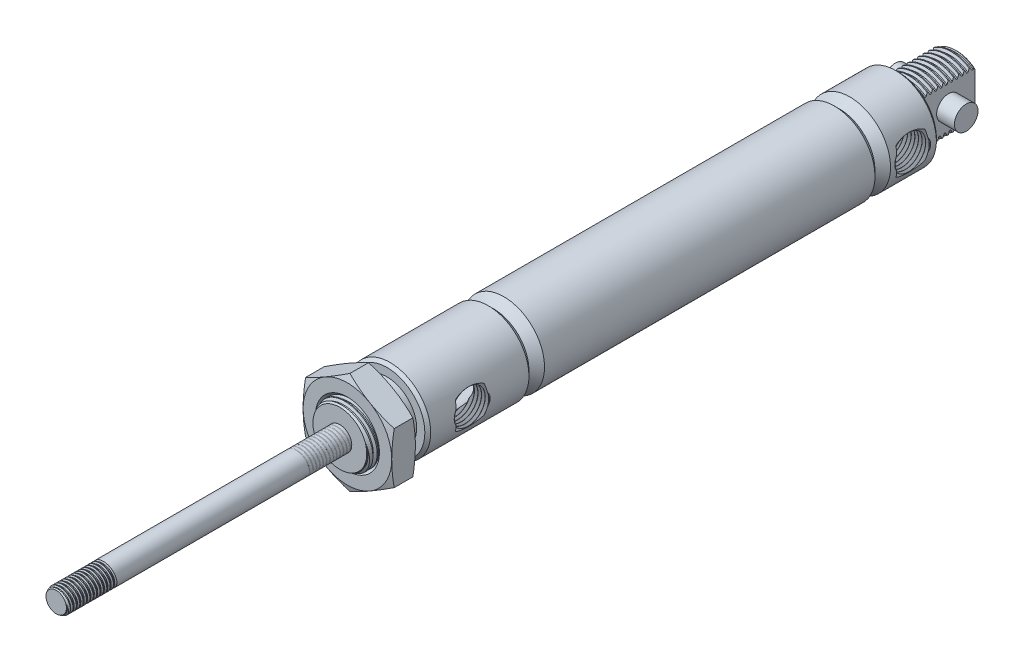
SolidWorks part; units mm, degrees
ref_plane "Front" through (0, 0, 0) normal (0, 0, 1) x (1, 0, 0)
ref_plane "Top" through (0, 0, 0) normal (0, 1, 0) x (1, 0, 0)
ref_plane "Right" through (0, 0, 0) normal (1, 0, 0) x (0, 0, -1)
sketch "Sketch1" plane through (0, 0, 0) normal (1, 0, 0) x (0, 0, -1)
  line L0 (-89.281, 0) -> (89.281, 0) construction
  line L1 (-76.581, -7.9375) -> (-76.581, 0) construction
  line L2 (-76.581, 7.9375) -> (-63.881, 7.9375) construction
  line L3 (-63.881, 0) -> (-63.881, 10.922)
  line L4 (-63.881, 10.922) -> (89.281, 10.922)
  line L5 (73.533, 10.922) -> (73.533, 7.9375) construction
  line L6 (73.533, 7.9375) -> (89.281, 7.9375) construction
  line L7 (89.281, 10.922) -> (89.281, 0)
  line L8 (89.281, 0) -> (105.029, 0) construction
  line L9 (-76.581, -7.9375) -> (-63.881, -7.9375) construction
  line L10 (-63.881, -7.9375) -> (-63.881, -10.922) construction
  line L11 (-63.881, -10.922) -> (89.281, -10.922) construction
  line L12 (73.533, -10.922) -> (73.533, -7.9375) construction
  line L13 (73.533, -7.9375) -> (89.281, -7.9375) construction
  line L14 (-66.167, 9.525) -> (-66.167, 0) construction
  line L18 (-76.581, 3.175) -> (-89.281, 3.175) construction
  line L19 (-89.281, 3.175) -> (-89.281, -3.175) construction
  line L20 (-89.281, -3.175) -> (-76.581, -3.175) construction
  line L24 (-76.581, 4.7625) -> (-66.167, 4.7625) construction
  line L25 (89.281, 0) -> (89.281, -10.922) construction
  line L26 (-76.581, 0) -> (-76.581, 7.9375) construction
  line L28 (-63.881, 0) -> (89.281, 0)
  line L29 (-71.374, 4.7625) -> (-71.374, 7.9375) construction
  line L30 (-63.881, 9.525) -> (-66.167, 9.525) construction
  dimension "D1" = 19.05
  dimension "J Flat" = 15.875
  dimension "E OD" = 21.844
  dimension "K Flat Depth" = 15.748
  dimension "RM Pilot" = 15.875
  dimension "G Pilot Length" = 12.7
  dimension "Shaft Dia" = 6.35
  dimension "A Thread Length" = 12.7
  dimension "Total Length" = 178.562
  dimension "V Pilot Length" = 2.286
revolve "Revolve1" add sketch "Sketch1" angle 360 about L8 reverse direction yes
sketch "Sketch58" plane through (0, 0, 0) normal (1, 0, 0) x (0, 0, -1)
  line L0 (89.281, 0) -> (105.029, 0) construction
  line L1 (73.533, 10.922) -> (89.281, 10.922)
  line L2 (73.533, 10.922) -> (73.533, 7.9375)
  line L3 (73.533, 7.9375) -> (89.281, 7.9375)
  line L4 (89.281, 10.922) -> (89.281, 7.9375)
  line L5 (89.281, 0) -> (105.029, 0) construction
revolve "Cut-Revolve25" cut sketch "Sketch58" angle 360 about L5
sketch "Sketch59" plane through (0, 0, -89.281) normal (0, 0, -1) x (-1, 0, 0)
  line L0 (-4.7625, -7.9375) -> (4.7625, 7.9375) construction
  line L1 (-4.7625, 7.9375) -> (4.7625, 7.9375)
  line L2 (-4.7625, 7.9375) -> (-4.7625, -7.9375)
  line L3 (-4.7625, -7.9375) -> (4.7625, -7.9375)
  line L4 (4.7625, 7.9375) -> (4.7625, -7.9375)
  dimension "D1" = 9.525
extrude "Cut-Extrude3" cut sketch "Sketch59" against normal up to surface (15.748 mm away) flip side to cut up to face at (7.9375, 0, -73.533)
chamfer "Chamfer1" distance 0.7874 angle 45 4 edges at (-10.922, 0, 63.881) (10.922, 0, -73.533) (0, 7.9375, -89.281) (0, -7.9375, -89.281)
sketch "Sketch4" plane through (0, 0, 0) normal (1, 0, 0) x (0, 0, -1)
  line L0 (-76.581, 0) -> (-76.581, 7.9375) construction
  line L1 (-89.281, 0) -> (89.281, 0) construction
  line L2 (-63.881, 0) -> (-63.881, 10.922) construction
  line L3 (-76.581, 7.9375) -> (-63.881, 7.9375) construction
  line L4 (-76.581, 0) -> (-76.581, 7.9375)
  line L5 (-76.581, 0) -> (-63.881, 0)
  line L6 (-63.881, 0) -> (-63.881, 7.9375)
  line L7 (-76.581, 7.9375) -> (-63.881, 7.9375)
  line L8 (-76.581, -7.9375) -> (-63.881, -7.9375) construction
  line L9 (-76.581, -7.9375) -> (-63.881, -7.9375) construction
revolve "Revolve2" add sketch "Sketch4" angle 360 about L5
sketch "Sketch5" plane through (0, 0, 0) normal (1, 0, 0) x (0, 0, -1)
  line L0 (-76.581, 7.9375) -> (-76.581, -7.9375) construction
  line L1 (-76.581, -7.9375) -> (-75.1699, -7.9375) construction
  line L2 (-75.1699, -7.9375) -> (-76.581, 7.9375) construction
  line L3 (-76.581, 7.9375) -> (-76.4053, 7.9531) construction
  line L4 (-76.4053, 7.9531) -> (-75.1754, 8.0624)
  line L5 (-75.1754, 8.0624) -> (-75.547, 7.2626)
  line L6 (-75.547, 7.2626) -> (-75.8984, 7.2314)
  line L7 (-75.8984, 7.2314) -> (-76.4053, 7.9531)
  line L8 (-75.7904, 8.0078) -> (-75.7227, 7.247) construction
  line L9 (-76.581, 7.9375) -> (-75.7841, 7.9375) construction
  line L10 (-75.7841, 7.9375) -> (-74.373, -7.9375) construction
  line L11 (-74.373, -7.9375) -> (-75.1699, -7.9375) construction
  line L12 (-76.581, 0) -> (-76.581, 7.9375) construction
  line L13 (-76.581, 7.9375) -> (-63.881, 7.9375) construction
  line L14 (-76.581, -7.9375) -> (-63.881, -7.9375) construction
  line L15 (-76.581, -0.1335) -> (-73.5761, 0.1335) construction
  point P19 (-75.0786, 0)
  dimension "D1" = 0.1764
  dimension "D2" = 0.3528
  dimension "Thread Pitch" = 1.4111
  dimension "D4" = 60
  dimension "D5" = 1.4111
revolve "Cut-Revolve2" cut sketch "Sketch5" angle 360 about L15
sketch "Sketch6" plane through (0, 0, 0) normal (1, 0, 0) x (0, 0, -1)
  line L0 (-76.581, 7.2314) -> (-75.358, 7.9375)
  line L1 (-75.358, 7.9375) -> (-76.581, 7.9375)
  line L2 (-76.581, 7.9375) -> (-76.581, 7.2314)
  line L3 (0, 0) -> (-76.581, 0) construction
  line L4 (-76.581, 0) -> (-76.581, 7.2314) construction
  line L5 (-76.581, 7.9375) -> (-63.881, 7.9375) construction
  line L6 (-76.581, 0) -> (-76.581, 7.9375) construction
  line L7 (-75.8984, 7.2314) -> (-76.581, 7.2314) construction
  dimension "D1" = 60
revolve "Cut-Revolve3" cut sketch "Sketch6" angle 360 about L3
pattern_linear "LPattern2" count 2 spacing 1.4111 along (0, 0, 1) count 9 spacing 1.4111 along (0, 0, -1) of "Cut-Revolve2"
sketch "Sketch53" plane through (0, 0, 0) normal (1, 0, 0) x (0, 0, -1)
  line L0 (-76.581, 0) -> (-63.881, 0) construction
  line L1 (-63.881, 7.9375) -> (-66.167, 7.9375)
  line L2 (-63.881, 7.9375) -> (-63.881, 0)
  line L3 (-63.881, 0) -> (-66.167, 0)
  line L4 (-66.167, 7.9375) -> (-66.167, 0)
  line L5 (-66.167, 9.525) -> (-66.167, 0) construction
  line L6 (-76.581, 7.9375) -> (-63.881, 7.9375) construction
  line L7 (-63.881, 0) -> (-63.881, 10.922) construction
revolve "Revolve4" add sketch "Sketch53" angle 360 about L3
sketch "Sketch62" plane through (0, 0, 0) normal (1, 0, 0) x (0, 0, -1)
  line L0 (73.533, 7.9375) -> (73.533, -7.9375) construction
  line L1 (73.533, -7.9375) -> (74.9441, -7.9375) construction
  line L2 (74.9441, -7.9375) -> (73.533, 7.9375) construction
  line L3 (73.533, 7.9375) -> (73.7087, 7.9531) construction
  line L4 (73.7087, 7.9531) -> (74.9386, 8.0624)
  line L5 (74.9386, 8.0624) -> (74.567, 7.2626)
  line L6 (74.567, 7.2626) -> (74.2156, 7.2314)
  line L7 (74.2156, 7.2314) -> (73.7087, 7.9531)
  line L8 (74.3913, 7.247) -> (74.3236, 8.0078) construction
  line L9 (73.533, 7.9375) -> (74.3299, 7.9375) construction
  line L10 (74.3299, 7.9375) -> (75.741, -7.9375) construction
  line L11 (75.741, -7.9375) -> (74.9441, -7.9375) construction
  line L12 (73.533, -0.1335) -> (76.5379, 0.1335) construction
  line L13 (73.533, 7.9375) -> (89.281, 7.9375) construction
  line L14 (73.533, 10.922) -> (73.533, 7.9375) construction
  line L15 (73.533, -7.9375) -> (89.281, -7.9375) construction
  point P13 (75.0354, 0)
  dimension "D1" = 60
  dimension "D2" = 0.3528
  dimension "D3" = 0.1764
  dimension "D4" = 1.4111
  dimension "D5" = 1.4111
revolve "Cut-Revolve26" cut sketch "Sketch62" angle 360 about L12
pattern_linear "LPattern5" count 11 spacing 1.4111 along (0, 0, -1) of "Cut-Revolve26"
sketch "Sketch60" plane through (0, 0, 0) normal (1, 0, 0) x (0, 0, -1)
  line L0 (-63.881, 0) -> (89.281, 0) construction
  line L1 (89.281, 10.922) -> (89.281, 0) construction
  circle A0 centre (82.169, 0) radius 3.175
  dimension "D2" = 6.35
  dimension "D1" = 7.112
extrude "Extrude2" add sketch "Sketch60" along normal mid plane 19.05
sketch "Sketch7" plane through (0, 0, 0) normal (1, 0, 0) x (0, 0, -1)
  line L0 (-76.581, 3.2004) -> (-60.706, 3.2004)
  line L1 (-60.706, 3.2004) -> (-60.706, 6.3627)
  line L2 (-60.706, 9.525) -> (-18.542, 9.525) construction
  line L3 (-12.192, 9.525) -> (51.308, 9.525)
  line L4 (51.308, 0) -> (-76.581, 0)
  line L5 (-76.581, 0) -> (-76.581, 3.2004)
  line L6 (-76.581, 0) -> (-76.581, 7.9375) construction
  line L7 (-63.881, 0) -> (89.281, 0) construction
  line L8 (51.308, 0) -> (105.029, 0) construction
  line L9 (-63.881, 0) -> (-63.881, 10.922) construction
  line L10 (51.308, 9.525) -> (51.308, 0)
  line L11 (56.261, 10.922) -> (57.658, 9.525)
  line L12 (-60.706, 6.3627) -> (-18.542, 6.3627)
  line L13 (-18.542, 6.3627) -> (-18.542, 9.525)
  line L14 (-60.706, 6.3627) -> (-60.706, 9.525) construction
  line L15 (-18.542, 9.525) -> (-12.192, 9.525)
  line L17 (57.658, 9.525) -> (57.658, 8.128)
  line L18 (57.658, 8.128) -> (60.452, 10.922)
  line L19 (60.452, 10.922) -> (56.261, 10.922)
  line L20 (57.658, 9.525) -> (57.658, 10.922) construction
  line L21 (-63.881, 10.922) -> (89.281, 10.922) construction
  line L22 (73.533, 10.922) -> (73.533, 7.9375) construction
  line L23 (-36.703, 10.922) -> (-35.306, 9.525)
  line L24 (-35.306, 9.525) -> (-35.306, 8.128)
  line L25 (-35.306, 8.128) -> (-32.512, 10.922)
  line L26 (-32.512, 10.922) -> (-36.703, 10.922)
  line L27 (-35.306, 9.525) -> (-35.306, 10.922) construction
  line L28 (-76.581, 3.175) -> (-89.281, 3.175) construction
  dimension "D1" = 0.0254
  dimension "Bore Dia" = 19.05
  dimension "D2" = 6.35
  dimension "D3" = 45
  dimension "Stroke" = 63.5
  dimension "D4" = 3.175
  dimension "D5" = 6.35
  dimension "D6" = 15.875
  dimension "D7" = 28.575
revolve "Cut-Revolve5" cut sketch "Sketch7" angle 360 about L8
sketch "Sketch8" plane through (0, 0, 0) normal (1, 0, 0) x (0, 0, -1)
  line L2 (44.958, 9.4742) -> (51.308, 9.4742)
  line L3 (51.308, 9.4742) -> (51.308, 0)
  line L4 (-89.281, 3.175) -> (-89.281, -3.175) construction
  line L6 (-89.281, 3.175) -> (-89.281, 0)
  line L7 (51.308, 0) -> (-89.281, 0)
  line L8 (-89.281, 0) -> (89.281, 0) construction
  line L9 (-12.192, 9.525) -> (51.308, 9.525) construction
  line L11 (51.308, 9.525) -> (51.308, 0) construction
  line L15 (44.958, 3.175) -> (44.958, 9.4742)
  line L16 (44.958, 3.175) -> (-89.281, 3.175)
  dimension "D1" = 0.0508
  dimension "D2" = 6.35
revolve "Revolve3" add sketch "Sketch8" angle 360 about L7
sketch "Sketch10" plane through (0, 0, 0) normal (1, 0, 0) x (0, 0, -1)
  line L0 (-89.281, 3.175) -> (-89.281, -3.175) construction
  line L1 (-89.281, -3.175) -> (-88.3739, -3.175) construction
  line L2 (-88.3739, -3.175) -> (-89.281, 3.175) construction
  line L3 (-89.281, 3.175) -> (-89.1687, 3.191) construction
  line L4 (-89.1687, 3.191) -> (-88.383, 3.3033)
  line L5 (-88.383, 3.3033) -> (-88.5942, 2.7771)
  line L6 (-88.5942, 2.7771) -> (-88.8187, 2.7451)
  line L7 (-88.8187, 2.7451) -> (-89.1687, 3.191)
  line L8 (-88.7759, 3.2472) -> (-88.7064, 2.7611) construction
  line L9 (-89.281, 3.175) -> (-88.7656, 3.175) construction
  line L10 (-88.7656, 3.175) -> (-87.8584, -3.175) construction
  line L11 (-87.8584, -3.175) -> (-88.3739, -3.175) construction
  line L12 (-89.281, 3.175) -> (-89.281, -3.175) construction
  line L13 (-76.581, 3.175) -> (-89.281, 3.175) construction
  line L14 (-89.281, -3.175) -> (-76.581, -3.175) construction
  line L15 (-89.281, -0.1384) -> (-87.343, 0.1384) construction
  point P19 (-88.312, 0)
  dimension "D1" = 0.1134
  dimension "D2" = 0.2268
  dimension "Shaft Thread Pitch" = 0.9071
  dimension "D4" = 0.9071
  dimension "D5" = 60
revolve "Cut-Revolve6" cut sketch "Sketch10" angle 360 about L15
sketch "Sketch11" plane through (0, 0, 0) normal (1, 0, 0) x (0, 0, -1)
  line L0 (-89.281, 3.175) -> (-88.5363, 3.175)
  line L1 (-88.5363, 3.175) -> (-89.281, 2.7451)
  line L2 (-89.281, 2.7451) -> (-89.281, 3.175)
  line L3 (0, 0) -> (-89.281, 0) construction
  line L4 (-89.281, 0) -> (-89.281, 2.7451) construction
  line L5 (-76.581, 3.175) -> (-89.281, 3.175) construction
  line L6 (-89.281, 3.175) -> (-89.281, -3.175) construction
  line L7 (-88.8187, 2.7451) -> (-89.281, 2.7451) construction
  dimension "D1" = 30
revolve "Cut-Revolve7" cut sketch "Sketch11" angle 360 about L3
pattern_linear "LPattern3" count 2 spacing 0.9071 along (0, 0, 1) count 14 spacing 0.9071 along (0, 0, -1) of "Cut-Revolve6"
pattern_linear "LPattern4" count 2 spacing 63.5 along (0, 0, 1) of bodies 122
ref_plane "Plane4" through (0, 0, -66.421) normal (0, 0, -1) x (-1, 0, 0)
ref_axis "Axis3" through (0, -15.123, -66.421) along (0, 1, 0)
ref_plane "Plane6" through (0, 0, -66.421) normal (0, 0, 1) x (1, 0, 0)
sketch "Sketch13" plane through (-356.4319, -1.7517, -66.421) normal (0, 0, 1) x (1, 0, 0)
  line L0 (355.9239, 1.7517) -> (355.9239, 5.9543)
  line L1 (355.9239, 5.9543) -> (356.3686, 6.7833) construction
  line L2 (356.3686, 6.7833) -> (356.8642, 5.9837) construction
  line L3 (356.8642, 5.9837) -> (357.3089, 6.8127) construction
  line L4 (357.3089, 6.8127) -> (357.8045, 6.013) construction
  line L5 (356.8811, 6.0153) -> (357.2919, 6.781)
  line L6 (357.2919, 6.781) -> (357.3278, 6.7822)
  line L7 (357.3278, 6.7822) -> (357.7856, 6.0435)
  line L8 (357.7856, 6.0435) -> (357.8214, 6.0446)
  line L9 (355.9239, 5.9543) -> (357.8045, 6.013) construction
  line L10 (356.3686, 6.7833) -> (357.3089, 6.8127) construction
  line L11 (356.1462, 6.3688) -> (357.5567, 6.4128) construction
  line L12 (355.9239, 1.7517) -> (351.7213, 1.7517) construction
  line L13 (357.8214, 6.0446) -> (358.2322, 6.8104)
  line L14 (355.9409, 5.9859) -> (356.3516, 6.7517)
  line L15 (356.3516, 6.7517) -> (356.3875, 6.7528)
  line L16 (356.3875, 6.7528) -> (356.8453, 6.0141)
  line L17 (356.8453, 6.0141) -> (356.8811, 6.0153)
  line L18 (356.1462, 6.3688) -> (355.9239, 6.3618) construction
  line L19 (355.9239, 6.3618) -> (355.9239, 5.9543) construction
  line L20 (356.1462, -2.8653) -> (355.9239, -2.8584) construction
  line L21 (355.9409, 5.9859) -> (355.9239, 5.9543)
  line L22 (358.2322, 6.8104) -> (358.268, 6.8116)
  line L23 (358.268, 6.8116) -> (358.7258, 6.0729)
  line L24 (358.7258, 6.0729) -> (358.7617, 6.074)
  line L25 (358.7617, 6.074) -> (359.1725, 6.8398)
  line L26 (359.1725, 6.8398) -> (359.2083, 6.8409)
  line L27 (359.2083, 6.8409) -> (359.6661, 6.1023)
  line L28 (359.6661, 6.1023) -> (359.702, 6.1034)
  line L29 (359.702, 6.1034) -> (360.1128, 6.8692)
  line L30 (360.1128, 6.8692) -> (360.1486, 6.8703)
  line L31 (360.1486, 6.8703) -> (360.6064, 6.1317)
  line L32 (360.6064, 6.1317) -> (360.6423, 6.1328)
  line L33 (360.6423, 6.1328) -> (361.053, 6.8986)
  line L34 (361.053, 6.8986) -> (361.0889, 6.8997)
  line L35 (361.0889, 6.8997) -> (361.5467, 6.1611)
  line L36 (361.5467, 6.1611) -> (361.5825, 6.1622)
  line L37 (361.5825, 6.1622) -> (361.9933, 6.928)
  line L38 (361.9933, 6.928) -> (362.0292, 6.9291)
  line L39 (362.0292, 6.9291) -> (362.487, 6.1904)
  line L40 (362.487, 6.1904) -> (362.5228, 6.1916)
  line L41 (362.5228, 6.1916) -> (362.9336, 6.9574)
  line L42 (362.9336, 6.9574) -> (362.9695, 6.9585)
  line L43 (362.9695, 6.9585) -> (363.4273, 6.2198)
  line L44 (363.4273, 6.2198) -> (363.4631, 6.221)
  line L45 (363.4631, 6.221) -> (363.8739, 6.9867)
  line L46 (363.8739, 6.9867) -> (363.9097, 6.9879)
  line L47 (363.9097, 6.9879) -> (364.3675, 6.2492)
  line L48 (364.3675, 6.2492) -> (364.4034, 6.2503)
  line L49 (364.4034, 6.2503) -> (364.8142, 7.0161)
  line L50 (364.8142, 7.0161) -> (364.85, 7.0173)
  line L51 (364.85, 7.0173) -> (365.3078, 6.2786)
  line L52 (365.3078, 6.2786) -> (365.3437, 6.2797)
  line L53 (365.3437, 6.2797) -> (365.7545, 7.0455)
  line L54 (365.7545, 7.0455) -> (365.7903, 7.0466)
  line L55 (365.7903, 7.0466) -> (366.2481, 6.308)
  line L56 (366.2481, 6.308) -> (366.284, 6.3091)
  line L57 (366.284, 6.3091) -> (366.6947, 7.0749)
  line L58 (366.6947, 7.0749) -> (366.7306, 7.076)
  line L59 (366.7306, 7.076) -> (367.1884, 6.3374)
  line L60 (367.1884, 6.3374) -> (367.2242, 6.3385)
  line L61 (367.2242, 6.3385) -> (367.635, 7.1043)
  line L62 (367.635, 7.1043) -> (367.6709, 7.1054)
  line L63 (367.6709, 7.1054) -> (368.1287, 6.3668)
  line L64 (368.1287, 6.3668) -> (368.1645, 6.3679)
  line L65 (368.1645, 6.3679) -> (368.5753, 7.1337)
  line L66 (368.5753, 7.1337) -> (368.6111, 7.1348)
  line L67 (368.6111, 7.1348) -> (369.0689, 6.3961)
  line L68 (369.0689, 6.3961) -> (369.1048, 6.3973)
  line L69 (369.1048, 6.3973) -> (369.5156, 7.1631)
  line L70 (369.5156, 7.1631) -> (369.5514, 7.1642)
  line L71 (369.5514, 7.1642) -> (370.0092, 6.4255)
  line L72 (370.0092, 6.4255) -> (370.0451, 6.4267)
  line L73 (355.9239, 1.7517) -> (370.0451, 1.7517)
  line L74 (370.0451, 1.7517) -> (370.0451, 6.4267)
  line L75 (356.3696, 6.7522) -> (356.3686, 6.7833) construction
  line L80 (356.4319, 1.7517) -> (367.3539, 1.7517) construction
  circle A0 centre (356.4319, 1.7517) radius 10.922 construction
  circle A1 centre (356.4319, 1.7517) radius 10.922 construction
  dimension "D1" = 60
  dimension "D2" = 0.031
  dimension "E0" = 9.2202
  dimension "D3" = 0.0359
  dimension "Thread Pitch" = 0.9407
  dimension "Thread Taper" = 3.58
  dimension "L4 Thread Length" = 11.43
revolve "Cut-Revolve22" cut sketch "Sketch13" angle 360 about L12
ref_plane "Plane7" through (0, 0, 51.943) normal (0, 0, 1) x (1, 0, 0)
sketch "Sketch64" plane through (-356.4319, -1.7517, 51.943) normal (0, 0, 1) x (1, 0, 0)
  line L0 (355.9239, 1.7517) -> (355.9239, 5.9543)
  line L1 (355.9239, 5.9543) -> (356.3686, 6.7833) construction
  line L2 (356.3686, 6.7833) -> (356.8642, 5.9837) construction
  line L3 (356.8642, 5.9837) -> (357.3089, 6.8127) construction
  line L4 (357.3089, 6.8127) -> (357.8045, 6.013) construction
  line L5 (356.8896, 6.0311) -> (357.2834, 6.7652)
  line L6 (357.2834, 6.7652) -> (357.3372, 6.7669)
  line L7 (357.3372, 6.7669) -> (357.7761, 6.0588)
  line L8 (357.7761, 6.0588) -> (357.8299, 6.0604)
  line L9 (355.9239, 5.9543) -> (357.8045, 6.013) construction
  line L10 (356.3686, 6.7833) -> (357.3089, 6.8127) construction
  line L11 (356.1462, 6.3688) -> (357.5567, 6.4128) construction
  line L12 (355.9239, 1.7517) -> (351.7213, 1.7517) construction
  line L13 (357.8299, 6.0604) -> (358.2237, 6.7946)
  line L14 (355.9493, 6.0017) -> (356.3432, 6.7359)
  line L15 (356.3432, 6.7359) -> (356.3969, 6.7375)
  line L16 (356.3969, 6.7375) -> (356.8358, 6.0294)
  line L17 (356.8358, 6.0294) -> (356.8896, 6.0311)
  line L18 (356.1462, 6.3688) -> (355.9239, 6.3618) construction
  line L19 (355.9239, 6.3618) -> (355.9239, 5.9543) construction
  line L20 (356.1462, -2.8653) -> (355.9239, -2.8584) construction
  line L21 (355.9493, 6.0017) -> (355.9239, 5.9543)
  line L22 (358.2237, 6.7946) -> (358.2775, 6.7963)
  line L23 (358.2775, 6.7963) -> (358.7164, 6.0882)
  line L24 (358.7164, 6.0882) -> (358.7702, 6.0898)
  line L25 (358.7702, 6.0898) -> (359.164, 6.824)
  line L26 (359.164, 6.824) -> (359.2178, 6.8257)
  line L27 (359.2178, 6.8257) -> (359.6567, 6.1175)
  line L28 (359.6567, 6.1175) -> (359.7105, 6.1192)
  line L29 (359.7105, 6.1192) -> (360.1043, 6.8534)
  line L30 (360.1043, 6.8534) -> (360.1581, 6.8551)
  line L31 (360.1581, 6.8551) -> (360.597, 6.1469)
  line L32 (360.597, 6.1469) -> (360.6507, 6.1486)
  line L33 (360.6507, 6.1486) -> (361.0446, 6.8828)
  line L34 (361.0446, 6.8828) -> (361.0983, 6.8845)
  line L35 (361.0983, 6.8845) -> (361.5372, 6.1763)
  line L36 (361.5372, 6.1763) -> (361.591, 6.178)
  line L37 (361.591, 6.178) -> (361.9849, 6.9122)
  line L38 (361.9849, 6.9122) -> (362.0386, 6.9139)
  line L39 (362.0386, 6.9139) -> (362.4775, 6.2057)
  line L40 (362.4775, 6.2057) -> (362.5313, 6.2074)
  line L41 (362.5313, 6.2074) -> (362.9251, 6.9416)
  line L42 (362.9251, 6.9416) -> (362.9789, 6.9432)
  line L43 (362.9789, 6.9432) -> (363.4178, 6.2351)
  line L44 (363.4178, 6.2351) -> (363.4716, 6.2368)
  line L45 (363.4716, 6.2368) -> (363.8654, 6.9709)
  line L46 (363.8654, 6.9709) -> (363.9192, 6.9726)
  line L47 (363.9192, 6.9726) -> (364.3581, 6.2645)
  line L48 (364.3581, 6.2645) -> (364.4119, 6.2661)
  line L49 (364.4119, 6.2661) -> (364.8057, 7.0003)
  line L50 (364.8057, 7.0003) -> (364.8595, 7.002)
  line L51 (364.8595, 7.002) -> (365.2984, 6.2938)
  line L52 (365.2984, 6.2938) -> (365.3521, 6.2955)
  line L53 (365.3521, 6.2955) -> (365.746, 7.0297)
  line L54 (365.746, 7.0297) -> (365.7997, 7.0314)
  line L55 (365.7997, 7.0314) -> (366.2387, 6.3232)
  line L56 (366.2387, 6.3232) -> (366.2924, 6.3249)
  line L57 (366.2924, 6.3249) -> (366.6863, 7.0591)
  line L58 (366.6863, 7.0591) -> (366.74, 7.0608)
  line L59 (366.74, 7.0608) -> (367.1789, 6.3526)
  line L60 (367.1789, 6.3526) -> (367.2327, 6.3543)
  line L61 (367.2327, 6.3543) -> (367.6265, 7.0885)
  line L62 (367.6265, 7.0885) -> (367.6803, 7.0902)
  line L63 (367.6803, 7.0902) -> (368.1192, 6.382)
  line L64 (368.1192, 6.382) -> (368.173, 6.3837)
  line L65 (368.173, 6.3837) -> (368.5668, 7.1179)
  line L66 (368.5668, 7.1179) -> (368.6206, 7.1196)
  line L67 (368.6206, 7.1196) -> (369.0595, 6.4114)
  line L68 (369.0595, 6.4114) -> (369.1133, 6.4131)
  line L69 (369.1133, 6.4131) -> (369.5071, 7.1473)
  line L70 (369.5071, 7.1473) -> (369.5609, 7.1489)
  line L71 (369.5609, 7.1489) -> (369.9998, 6.4408)
  line L72 (369.9998, 6.4408) -> (370.0536, 6.4425)
  line L73 (355.9239, 1.7517) -> (370.0536, 1.7517)
  line L74 (370.0536, 1.7517) -> (370.0536, 6.4425)
  line L75 (356.37, 6.7367) -> (356.3686, 6.7833) construction
  line L80 (356.4319, 1.7517) -> (367.3539, 1.7517) construction
  circle A1 centre (356.4319, 1.7517) radius 10.922 construction
  circle A2 centre (356.4319, 1.7517) radius 10.922 construction
  dimension "D1" = 60
  dimension "D2" = 0.0466
  dimension "D3" = 0.0538
  dimension "Thread Pitch" = 0.9407
  dimension "D4" = 9.2202
  dimension "Thread Taper" = 3.58
  dimension "L4 Thread Length" = 11.43
revolve "Cut-Revolve27" cut sketch "Sketch64" angle 360 about L73
ref_plane "Plane2" through (0, 0, 71.374) normal (0, 0, 1) x (1, 0, 0)
sketch "Sketch54" plane through (0, 0, 71.374) normal (0, 0, 1) x (1, 0, 0)
  line L1 (0, 13.7482) -> (-11.9062, 6.8741)
  line L2 (-11.9062, 6.8741) -> (-11.9062, -6.8741)
  line L3 (-11.9062, -6.8741) -> (0, -13.7482)
  line L4 (0, -13.7482) -> (11.9062, -6.8741)
  line L5 (11.9062, -6.8741) -> (11.9062, 6.8741)
  line L6 (11.9062, 6.8741) -> (0, 13.7482)
  circle A0 centre (0, 0) radius 11.9062 construction
  circle A1 centre (0, 0) radius 7.9375
  dimension "Nut Hex" = 23.8125
extrude "Extrude1" add sketch "Sketch54" along normal mid plane 6.35 separate body
sketch "Sketch55" plane through (0, 0, 0) normal (1, 0, 0) x (0, 0, -1)
  line L0 (-73.8786, 13.7482) -> (-74.549, 13.7482)
  line L1 (-74.549, 13.7482) -> (-74.549, 11.9062)
  line L2 (-74.549, 11.9062) -> (-73.8786, 13.7482)
  line L3 (-68.8694, 13.7482) -> (-68.199, 13.7482)
  line L4 (-68.199, 13.7482) -> (-68.199, 11.9062)
  line L5 (-68.199, 11.9062) -> (-68.8694, 13.7482)
  line L6 (-74.549, 11.9062) -> (-68.199, 11.9062) construction
  line L7 (-74.549, 13.7482) -> (-68.199, 13.7482) construction
  line L10 (0, 0) -> (-74.549, 0) construction
  line L11 (-74.549, 0) -> (-74.549, 11.9062) construction
  line L12 (-74.549, 8.6079) -> (-74.549, 7.9375)
  line L13 (-74.549, 7.9375) -> (-73.8786, 7.9375)
  line L14 (-73.8786, 7.9375) -> (-74.549, 8.6079)
  line L15 (-68.199, 8.6079) -> (-68.199, 7.9375)
  line L16 (-68.199, 7.9375) -> (-68.8694, 7.9375)
  line L17 (-68.8694, 7.9375) -> (-68.199, 8.6079)
  line L19 (-73.8786, 13.7482) -> (-73.8786, 7.9375) construction
  line L20 (-68.199, 6.8741) -> (-68.199, 13.7482) construction
  line L21 (-74.549, 6.8741) -> (-74.549, 13.7482) construction
  line L22 (-68.199, 7.9375) -> (-74.549, 7.9375) construction
  dimension "D1" = 20
  dimension "D2" = 23.8125
  dimension "D3" = 45
revolve "Cut-Revolve24" cut sketch "Sketch55" angle 360 about L10
equation "\"D1@Chamfer1\"=\"K Flat Depth@Sketch1\"/20"
equation "\"D1@Sketch5\"=\"Thread Pitch@Sketch5\"/8"
equation "\"D2@Sketch5\"=\"Thread Pitch@Sketch5\"/4"
equation "\"D5@Sketch5\"=\"Thread Pitch@Sketch5\""
equation "\"D3@LPattern2\"=\"Thread Pitch@Sketch5\""
equation "\"D4@LPattern2\"=\"Thread Pitch@Sketch5\""
equation "\"D2@LPattern2\"=\"G Pilot Length@Sketch1\"/\"Thread Pitch@Sketch5\""
equation "\"D1@Sketch10\"=\"Shaft Thread Pitch@Sketch10\"/8"
equation "\"D2@Sketch10\"=\"Shaft Thread Pitch@Sketch10\"/4"
equation "\"D4@Sketch10\"=\"Shaft Thread Pitch@Sketch10\""
equation "\"D3@LPattern3\"=\"Shaft Thread Pitch@Sketch10\""
equation "\"D4@LPattern3\"=\"Shaft Thread Pitch@Sketch10\""
equation "\"D2@LPattern3\"=\"A Thread Length@Sketch1\"/\"Shaft Thread Pitch@Sketch10\""
equation "\"D3@LPattern4\"=\"Stroke@Sketch7\""
equation "\"D2@Sketch13\"=\"Thread Pitch@Sketch13\"*.033"
equation "\"D2@Sketch55\"=\"Nut Hex@Sketch54\""
equation "\"D3@Sketch62\"=\"D4@Sketch62\"/8"
equation "\"D2@Sketch62\"=\"D4@Sketch62\"/4"
equation "\"D5@Sketch62\"=\"D4@Sketch62\""
equation "\"D4@Sketch62\"=\"Thread Pitch@Sketch5\""
equation "\"D3@LPattern5\"=\"Thread Pitch@Sketch5\""
equation "\"D1@LPattern5\"=\"K Flat Depth@Sketch1\"/\"Thread Pitch@Sketch5\""
